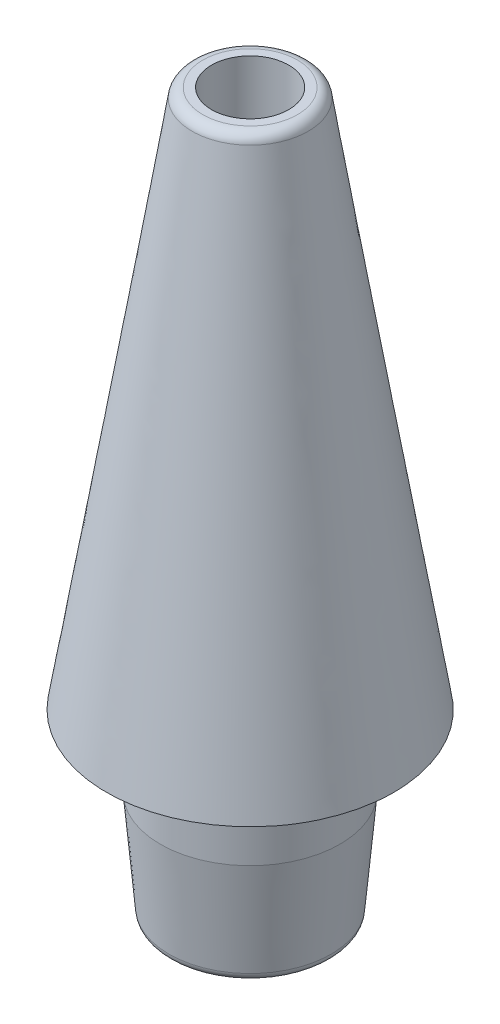
SolidWorks part; units mm, degrees
material "ABS"
ref_plane "Front Plane" through (0, 0, 0) normal (0, 0, 1) x (1, 0, 0)
ref_plane "Top Plane" through (0, 0, 0) normal (0, 1, 0) x (1, 0, 0)
ref_plane "Right Plane" through (0, 0, 0) normal (1, 0, 0) x (0, 0, -1)
sketch "Sketch1" plane through (0, 0, 0) normal (0, 1, 0) x (1, 0, 0)
  circle A0 centre (0, 0) radius 2.5
  dimension "D1" = 5
extrude "Boss-Extrude1" add sketch "Sketch1" along normal blind 5
sketch "Sketch2" plane through (0, 5, 0) normal (0, 1, 0) x (1, 0, 0)
  circle A0 centre (0, 0) radius 4
  dimension "D1" = 8
ref_plane "Plane1" through (0, 20, 0) normal (0, 1, 0) x (1, 0, 0)
sketch "Sketch3" plane through (0, 20, 0) normal (0, 1, 0) x (1, 0, 0)
  circle A0 centre (0, 0) radius 1.575
  circle A1 centre (0, 0) radius 1.075 construction
  dimension "D1" = 0.5
  dimension "D2" = 2.15
loft "Loft1" add profiles "Sketch3", "Sketch2" connector at (-1.3924, 20, -0.7361) connector at (-3.844, 5, -1.1063)
sketch "Sketch4" plane through (0, 20, 0) normal (0, 1, 0) x (1, 0, 0)
  circle A0 centre (0, 0) radius 1.075
  dimension "D1" = 2.15
extrude "Cut-Extrude1" cut sketch "Sketch4" against normal through all
chamfer "Chamfer1" distance 0.3 angle 88 1 edges at (0, 0, 1.075) first distance on face at (0, 0, 1.075)
chamfer "Chamfer2" distance 3 angle 5 1 edges at (0, 0, 2.5) first distance on face at (0, 5, 2.5)
fillet "Fillet1" radius 0.3 1 edges at (0, 20, 1.575)
fillet "Fillet2" radius 0.25 1 edges at (0, 5, 2.5)
fillet "Fillet4" radius 0.25 2 edges at (0, 0, 1.375) (0, 0, 2.2375)
